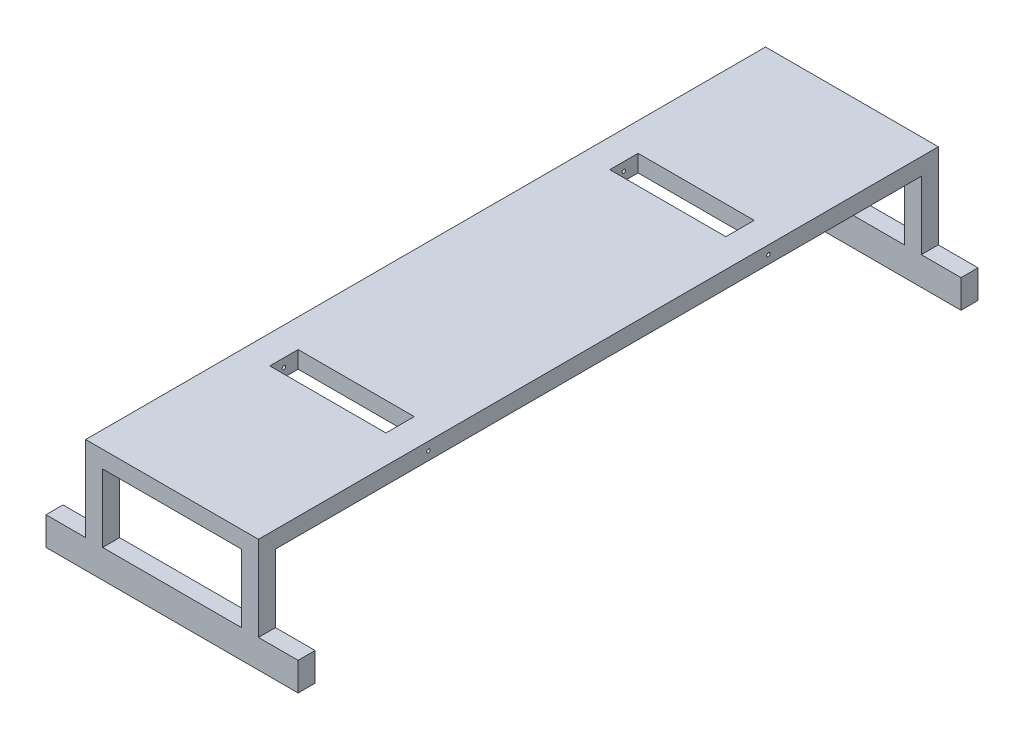
SolidWorks part; units mm, degrees
ref_plane "Front Plane" through (0, 0, 0) normal (0, 0, 1) x (1, 0, 0)
ref_plane "Top Plane" through (0, 0, 0) normal (0, 1, 0) x (1, 0, 0)
ref_plane "Right Plane" through (0, 0, 0) normal (1, 0, 0) x (0, 0, -1)
sketch "Sketch1" plane through (0, 0, 0) normal (0, 0, 1) x (1, 0, 0)
  line L0 (0, -1000) -> (0, 0) construction
  line L1 (0, 0) -> (169.9874, 0) construction
  line L2 (-152.5, 57.6054) -> (-152.5, -45.7757) construction
  line L3 (-222.5, 48.8617) -> (-222.5, -61.2057) construction
  line L4 (-119.8645, 150) -> (85.7528, 150) construction
  line L5 (-248.3753, -50) -> (-62.4829, -50) construction
  line L6 (-122.5, 75.845) -> (-122.5, 42.1608) construction
  line L7 (222.5, -50) -> (-222.5, -50)
  line L8 (-222.5, -50) -> (-222.5, 0)
  line L9 (-222.5, 0) -> (-152.5, 0)
  line L10 (-152.5, 0) -> (-152.5, 150)
  line L11 (-152.5, 150) -> (152.5, 150)
  line L12 (-100.5433, 120) -> (-26.2786, 120) construction
  line L13 (-122.5, 0) -> (-122.5, 120)
  line L14 (-122.5, 120) -> (122.5, 120)
  line L15 (122.5, 0) -> (-122.5, 0)
  line L16 (122.5, 0) -> (122.5, 120)
  line L17 (152.5, 0) -> (152.5, 150)
  line L18 (222.5, 0) -> (152.5, 0)
  line L19 (222.5, -50) -> (222.5, 0)
  line L20 (0, 120) -> (0, 142.9848) construction
  line L21 (-152.5, 0) -> (-122.5, 0)
  line L22 (122.5, 0) -> (152.5, 0)
  point P30 (0, 0)
  point P31 (0, 120)
  point P32 (0, 150)
  point P35 (0, -50)
  dimension "D1" = 152.5
  dimension "D2" = 70
  dimension "D3" = 150
  dimension "D4" = 50
  dimension "D5" = 30
  dimension "D6" = 30
extrude "Boss-Extrude1" add sketch "Sketch1" along normal blind 1200 contours L22 L15 L21 L9 L8 L7 L19 L18 region at (0, -25, 0)
extrude "Boss-Extrude2" add sketch "Sketch1<3>" along normal blind 1200 contours L16 L22 L17 L11 L10 L21 L13 L14 region at (137.5, 3.3989, 0)
sketch "Sketch1<3>" plane through (0, 0, 0) normal (0, 0, 1) x (1, 0, 0) same geometry as "Sketch1"
sketch "Sketch2" plane through (0, 0, 0) normal (1, 0, 0) x (0, 0, -1)
  line L0 (0, 0) -> (0, 175.8488) construction
  line L1 (0, 0) -> (-96.0031, 0) construction
  line L2 (-30, 161.1577) -> (-30, -68.8605) construction
  line L3 (-1200, 11.9542) -> (-1200, 332.6054) construction
  line L5 (-1170, 190.8438) -> (-1170, -121.9318) construction
  line L6 (-1119.3158, 150) -> (-1269.4322, 150) construction
  line L8 (-1227.6141, 120) -> (-991.7169, 120) construction
  line L9 (-1170, 0) -> (-1170, 120)
  line L10 (-1170, 120) -> (-30, 120)
  line L11 (-30, 120) -> (-30, 0)
  line L12 (-30, 0) -> (-1170, 0)
  dimension "D1" = 30
  dimension "D2" = 1200
  dimension "D3" = 30
  dimension "D4" = 30
extrude "Cut-Extrude1" cut sketch "Sketch2" against normal through all and the other way through all
sketch "Sketch3" plane through (0, 0, 0) normal (0, 1, 0) x (1, 0, 0)
  line L0 (0, 0) -> (-475.0064, 0) construction
  line L1 (0, 0) -> (0, 318.9409) construction
  line L2 (-289.8178, -30) -> (358.4811, -30) construction
  line L3 (-62.513, -1200) -> (-393.8658, -1200) construction
  line L4 (-152.5, -30) -> (-222.5, -30)
  line L5 (-635.5772, -1170) -> (-315.2838, -1170) construction
  line L6 (-222.5, -30) -> (-222.5, -1170)
  line L7 (-152.5, -1139.2337) -> (-152.5, -1271.6929) construction
  line L8 (152.5, -1116.8912) -> (152.5, -1263.7134) construction
  line L9 (-222.5, -1200) -> (-222.5, 0) construction
  line L10 (-152.5, -1170) -> (152.5, -1170)
  line L12 (152.5, -30) -> (-152.5, -30)
  line L14 (-222.5, -1170) -> (-152.5, -1170)
  line L15 (152.5, -30) -> (222.5, -30)
  line L16 (222.5, -30) -> (222.5, -1170)
  line L17 (222.5, -1200) -> (222.5, 0) construction
  line L18 (222.5, -1170) -> (152.5, -1170)
  dimension "D1" = 30
  dimension "D2" = 1200
  dimension "D3" = 30
  dimension "D4" = 152.5
  dimension "D5" = 152.5
extrude "Cut-Extrude3" cut sketch "Sketch3" against normal through all
sketch "Sketch4" plane through (0, 0, 0) normal (0, 1, 0) x (1, 0, 0)
  line L0 (0, 0) -> (-502.7135, 0) construction
  line L1 (-732.6587, -900) -> (-176.512, -900) construction
  line L2 (0, 0) -> (0, -734.4874) construction
  line L3 (-45.5717, -1200) -> (-428.625, -1200) construction
  line L5 (0, -600) -> (-538.9696, -600) construction
  line L6 (-778.5749, -300) -> (-269.4136, -300) construction
  line L7 (102.5, -925) -> (-102.5, -925)
  line L8 (102.5, -325) -> (-102.5, -325)
  line L9 (102.5, -325) -> (102.5, -275)
  line L10 (102.5, -275) -> (-102.5, -275)
  line L11 (-102.5, -325) -> (-102.5, -275)
  line L12 (102.5, -325) -> (-102.5, -275) construction
  line L13 (102.5, -275) -> (-102.5, -325) construction
  line L18 (102.5, -925) -> (102.5, -875)
  line L19 (102.5, -875) -> (-102.5, -875)
  line L20 (-102.5, -925) -> (-102.5, -875)
  line L21 (102.5, -925) -> (-102.5, -875) construction
  line L22 (102.5, -875) -> (-102.5, -925) construction
  point P11 (0, -300)
  point P18 (0, -900)
  dimension "D1" = 600
  dimension "D2" = 300
  dimension "D3" = 50
  dimension "D4" = 205
  dimension "D5" = 300
  dimension "D6" = 50
  dimension "D7" = 205
extrude "Cut-Extrude4" cut sketch "Sketch4" along normal through all
sketch "Sketch5" plane through (0, 0, 0) normal (1, 0, 0) x (0, 0, -1)
  line L0 (0, 0) -> (-667.1627, 0) construction
  line L1 (0, 0) -> (0, 357.7733) construction
  line L2 (-1200, 19.1794) -> (-1200, 343.4122) construction
  line L4 (-600, 465.4617) -> (-600, -139.8549) construction
  line L5 (-900, 242.3206) -> (-900, -157.1145) construction
  line L6 (-300, 280.5381) -> (-300, -72.0496) construction
  line L7 (-1234.568, 135) -> (-730.1719, 135) construction
  line L8 (-1170, 120) -> (-30, 120) construction
  circle A0 centre (-900, 135) radius 3.05
  circle A1 centre (-300, 135) radius 3.05
  point P20 (0, 0)
  dimension "D6" = 6.1
  dimension "D7" = 6.1
  dimension "D1" = 1200
  dimension "D2" = 600
  dimension "D3" = 300
  dimension "D4" = 300
  dimension "D5" = 15
extrude "Cut-Extrude5" cut sketch "Sketch5" against normal through all and the other way through all
equation "\"D1@Sketch4\"=1200/2"
